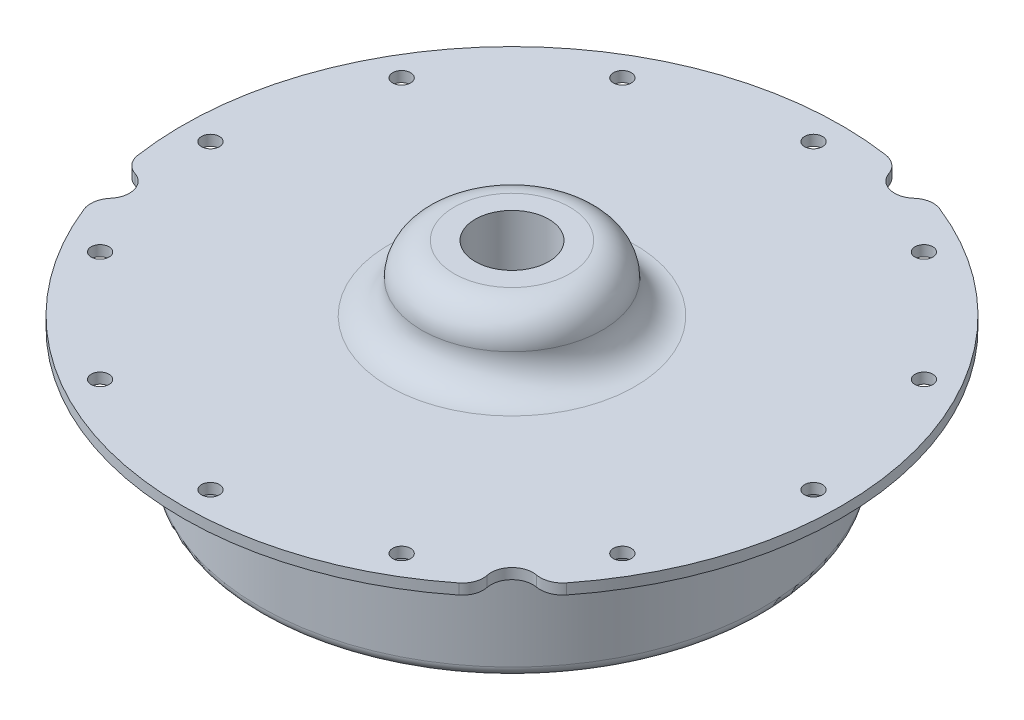
SolidWorks part; units mm, degrees
material "6063-T6"
ref_plane "Front Plane" through (0, 0, 0) normal (0, 0, 1) x (1, 0, 0)
ref_plane "Top Plane" through (0, 0, 0) normal (0, 1, 0) x (1, 0, 0)
ref_plane "Right Plane" through (0, 0, 0) normal (1, 0, 0) x (0, 0, -1)
ref_axis "Axis1" through (0, 55, 0) along (0, -1, 0)
sketch "Sketch1" plane through (0, 0, 0) normal (0, 0, 1) x (1, 0, 0)
  line L0 (-49.784, 0) -> (-41.275, 0)
  line L1 (0, 55) -> (0, -55) construction
  line L2 (-49.784, 0) -> (-49.784, 1.5875)
  line L3 (-5.5562, 11.43) -> (-8.7312, 11.43)
  line L5 (-5.5562, 11.43) -> (-5.5562, 0)
  line L6 (-5.5562, 0) -> (0, 0) construction
  line L7 (-49.784, 0) -> (-49.784, 1.5875) construction
  line L8 (-5.5562, 1.5875) -> (-5.5562, 0) construction
  line L9 (-38.1, -3.175) -> (-38.1, -17.4625)
  line L11 (-34.925, -17.4625) -> (-34.925, -3.175)
  line L12 (-31.75, 0) -> (-5.5562, 0)
  line L13 (0, -201000) -> (0, 249000) construction
  line L14 (-49.784, 1.5875) -> (-18.5737, 1.5875)
  arc A0 (-34.925, -3.175) -> (-31.75, 0) centre (-31.75, -3.175) cw
  arc A1 (-38.1, -3.175) -> (-41.275, 0) centre (-41.275, -3.175) ccw
  arc A2 (-18.5737, 1.5875) -> (-13.6525, 6.5088) centre (-18.5737, 6.5088) ccw
  arc A3 (-8.7312, 11.43) -> (-13.6525, 6.5088) centre (-8.7312, 6.5088) ccw
  arc A4 (-38.1, -17.4625) -> (-34.925, -17.4625) centre (-36.5125, -17.4625) ccw
  point P18 (-34.925, 0)
  dimension "D4" = 3.175
  dimension "D5" = 3.175
  dimension "D1" = 3.175
  dimension "D2" = 38.1
  dimension "D3" = 17.4625
  dimension "D6" = 1.5875
  dimension "D7" = 3.175
  dimension "D8" = 11.43
revolve "Revolve1" add sketch "Sketch1" angle 360 about axis through (0, 55, 0) along (0, -1, 0)
ref_plane "Hole Location Plane" through (0, 3.175, 0) normal (0, 1, 0) x (1, 0, 0)
sketch "Hole Location" plane through (0, 3.175, 0) normal (0, 1, 0) x (1, 0, 0)
  line L0 (0, 0) -> (-45.5549, 0) construction
  circle A0 centre (0, 0) radius 45.5549 construction
  point P3 (0, 0)
  dimension "D1" = 91.1098
hole_wizard "#36 (0.1065) Diameter Hole1" positions "Sketch2" profile "Sketch3" hole size "#36" standard "ANSI Inch" end condition through all
sketch "Sketch2" plane through (0, 1.5875, 0) normal (0, 1, 0) x (1, 0, 0)
  point P0 (-45.5549, 0)
sketch "Sketch3" plane through (-45.5549, 1.5875, 0) normal (1, 0, 0) x (0, 0, 1)
  line L0 (0, 0) -> (0, 20.6375)
  line L1 (0, 20.6375) -> (1.3525, 20.6375)
  line L2 (1.3525, 20.6375) -> (1.3525, 0)
  line L5 (1.3525, 0) -> (0, 0)
  line L11 (0, -6.35) -> (0, 107.95) construction
  dimension "Thru Hole Dia." = 2.7051
  dimension "Thru Hole Depth" = 20.6375
pattern_circular "CirPattern1" count 12 over 360 of "#36 (0.1065) Diameter Hole1"
hole_wizard "7/16 (0.4375) Diameter Hole1" positions "Sketch4" profile "Sketch5" hole size "7/16" standard "ANSI Inch" end condition through all
sketch "Sketch4" plane through (0, 11.43, 0) normal (0, 1, 0) x (1, 0, 0)
  point P0 (0, 0)
sketch "Sketch5" plane through (0, 11.43, 0) normal (1, 0, 0) x (0, 0, 1)
  line L0 (0, 0) -> (0, 30.48)
  line L1 (0, 30.48) -> (5.5562, 30.48)
  line L2 (5.5562, 30.48) -> (5.5562, 0)
  line L5 (5.5562, 0) -> (0, 0)
  line L11 (0, -6.35) -> (0, 107.95) construction
  dimension "Thru Hole Dia." = 11.1125
  dimension "Thru Hole Depth" = 30.48
sketch "Sketch6" plane through (0, 1.5875, 0) normal (0, 1, 0) x (1, 0, 0)
  line L0 (0, 0) -> (-48.0877, -12.885) construction
  line L1 (0, 0) -> (-45.5549, 0) construction
  circle A0 centre (0, 0) radius 49.784 construction
  arc A1 (-49.2429, -7.3202) -> (-47.095, -9.8692) centre (-46.1024, -6.8534) ccw
  arc A2 (-47.095, -9.8692) -> (-45.6723, -14.9458) centre (-48.0877, -12.885) cw
  circle A3 centre (0, 0) radius 49.784 construction
  arc A4 (-45.6723, -14.9458) -> (-46.2472, -18.4294) centre (-43.0722, -17.1641) ccw
  arc A5 (-46.2472, -18.4294) -> (-49.2429, -7.3202) centre (0, 0) cw
  arc A6 (9.8927, 47.0263) -> (7.1633, 49.2659) centre (6.6715, 45.8837) ccw
  arc A7 (15.0005, 45.7201) -> (9.8927, 47.0263) centre (12.885, 48.0877) cw
  arc A8 (18.282, 46.3057) -> (15.0005, 45.7201) centre (17.116, 43.3525) ccw
  arc A9 (7.1633, 49.2659) -> (18.282, 46.3057) centre (0, 0) cw
  arc A10 (35.7796, -32.0805) -> (39.0839, -30.8366) centre (36.4007, -28.7196) ccw
  arc A11 (32.0945, -35.8509) -> (35.7796, -32.0805) centre (35.2026, -35.2026) cw
  arc A12 (30.9609, -38.9855) -> (32.0945, -35.8509) centre (28.9864, -36.4992) ccw
  arc A13 (39.0839, -30.8366) -> (30.9609, -38.9855) centre (0, 0) cw
  point P31 (0, 0)
  circle M16 centre (0, 0) radius 49.784
  dimension "D2" = 3.175
  dimension "D3" = 3.175
  dimension "D4" = 49.784
  dimension "D5" = 3.175
  dimension "D1" = 15
  dimension "D6" = 3
extrude "Cut-Extrude1" cut sketch "Sketch6" against normal up to surface (1.5875 mm away) contours L0 | A4 A2 A1 M16 | A12 A10 A11 M16 | A7 A6 A9 A8 region at (-46.8529, 1.5875, 12.5779) region at (34.3192, 1.5875, 34.2869) up to face at (-39.4517, 0, -24.13)
equation "\"D1@Hole Location\"=\"TANK DIAMETER@Cryo Tank.Assembly\"+\"GASKET SEAT THICKNESS@Cryo Tank.Assembly\"+\"LINER THICKNESS@Cryo Tank.Assembly\"+\"SHRINK FIT DELTA@Cryo Tank.Assembly\""
equation "\"D2@Sketch1\"=\"TANK DIAMETER@Cryo Tank.Assembly\"/2"
equation "\"D3@Sketch1\"=0.5+0.125+0.0625"
